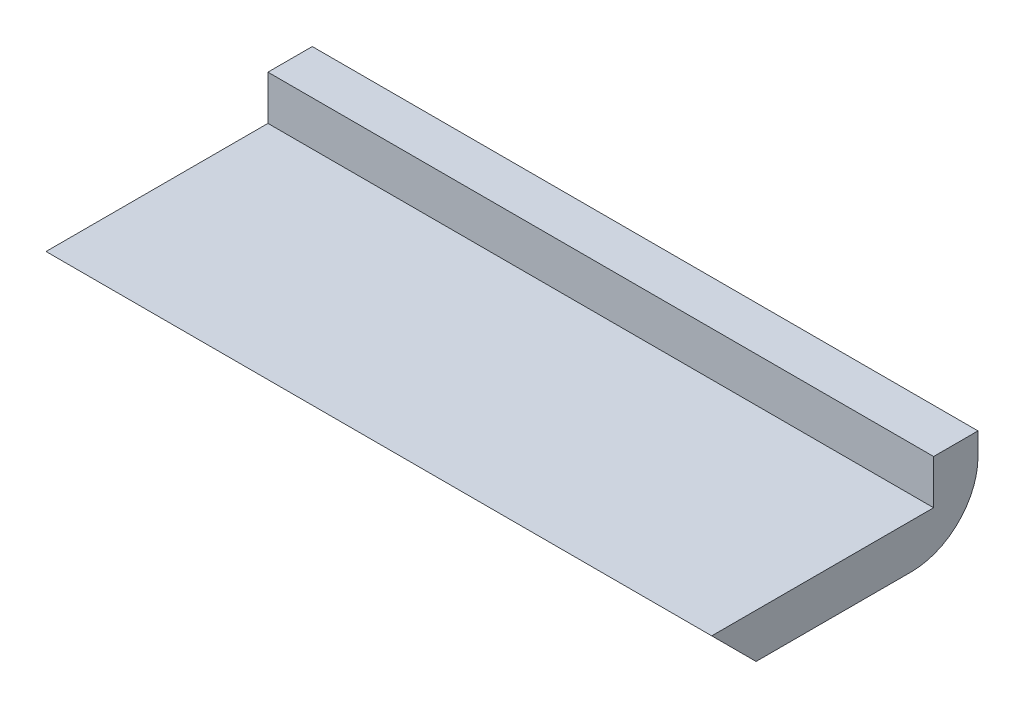
SolidWorks part; units mm, degrees
ref_plane "Alzado" through (0, 0, 0) normal (0, 0, 1) x (1, 0, 0)
ref_plane "Planta" through (0, 0, 0) normal (0, 1, 0) x (1, 0, 0)
ref_plane "Vista lateral" through (0, 0, 0) normal (1, 0, 0) x (0, 0, -1)
sketch "Croquis1" plane through (0, 0, 0) normal (0, 1, 0) x (1, 0, 0)
  line L1 (-15, -5) -> (15, -5)
  line L2 (-15, -5) -> (-15, 5)
  line L3 (-15, 5) -> (15, 5)
  line L4 (15, -5) -> (15, 5)
  line L5 (-15, -5) -> (15, 5) construction
  line L6 (-15, 5) -> (15, -5) construction
  point P0 (0, 0)
extrude "Saliente-Extruir1" add sketch "Croquis1" along normal blind 2
sketch "Croquis2" plane through (0, 2, 0) normal (0, 1, 0) x (1, 0, 0)
  line L1 (-15, 5) -> (15, 5)
  line L2 (-15, 5) -> (-15, 7)
  line L3 (-15, 7) -> (15, 7)
  line L4 (15, 5) -> (15, 7)
extrude "Saliente-Extruir2" add sketch "Croquis2" along normal blind 2 and the other way blind 2
sketch "Croquis3" plane through (0, 0, 0) normal (0, -1, 0) x (1, 0, 0)
  line L0 (0, -7) -> (0, -5)
  line L1 (15, -7) -> (-15, -7) construction
  line L2 (0, 5) -> (0, 3)
  line L3 (-15, 5) -> (15, 5) construction
  line L4 (-13, 3) -> (13, 3)
  line L5 (13, 3) -> (13, -5)
  line L6 (13, -5) -> (-13, -5)
  line L7 (-13, -5) -> (-13, 3)
  line L8 (-108.2504, -345.5802) -> (-588.2504, -345.5802) construction
  line L9 (15, 5) -> (15, -7) construction
  line L10 (-15, -7) -> (-15, 5) construction
  line L11 (-107.2449, -345.9043) -> (-587.2449, -345.9043) construction
  line L12 (-13, -3.3986) -> (-13, 1.6832)
  line L13 (-13, 1.6832) -> (-11.8002, 1.6832)
  line L14 (-11.8002, 1.6832) -> (-9.5832, -1.3407)
  line L15 (-9.5832, -1.3407) -> (-10.2334, -2.2573)
  line L16 (-10.2334, -2.2573) -> (-11.7241, -0.2241)
  line L17 (-11.7241, -0.2241) -> (-11.7241, -3.3986)
  line L18 (-11.7241, -3.3986) -> (-13, -3.3986)
  line L19 (-8.709, 1.6832) -> (-7.5492, 1.6832)
  line L20 (-7.5492, 1.6832) -> (-7.5492, -3.3986)
  line L21 (-7.5492, -3.3986) -> (-8.83, -3.3986)
  line L22 (-8.83, -3.3986) -> (-8.83, -0.2241)
  line L23 (-8.83, -0.2241) -> (-9.3309, -0.9303)
  line L24 (-9.3309, -0.9303) -> (-9.9615, -0.0702)
  line L25 (-9.9615, -0.0702) -> (-8.709, 1.6832)
  line L26 (-6.6004, 1.6832) -> (-5.3492, 1.6832)
  line L27 (-5.3492, 1.6832) -> (-5.3492, -1.7252)
  line L28 (-1.4166, 1.6832) -> (-0.3542, 1.6832)
  line L29 (-0.3542, 1.6832) -> (3.0735, -2.8639)
  line L30 (-6.6004, 1.6832) -> (-6.6004, -1.7252)
  line L31 (-3.5616, 1.6832) -> (-2.3179, 1.6832)
  line L32 (-2.3179, 1.6832) -> (-2.3179, -1.7252)
  line L33 (-3.5616, 1.6832) -> (-3.5616, -1.7252)
  line L34 (3.0735, -2.8639) -> (3.0735, -3.4119)
  line L35 (3.0735, -3.4119) -> (2.0041, -3.4119)
  line L36 (2.0041, -3.4119) -> (-1.4166, 1.126)
  line L37 (-1.4166, 1.126) -> (-1.4166, 1.6832)
  line L38 (-1.4166, -3.4119) -> (-0.1476, -3.4119)
  line L39 (-0.1476, -3.4119) -> (-0.1476, -1.1658)
  line L40 (-0.1476, -1.1658) -> (-1.4166, 0.4548)
  line L41 (-1.4166, 0.4548) -> (-1.4166, -3.4119)
  line L42 (1.8742, 1.6832) -> (3.0735, 1.6832)
  line L43 (3.0735, 1.6832) -> (3.0735, -2.084)
  line L44 (3.0735, -2.084) -> (1.8742, -0.5524)
  line L45 (1.8742, -0.5524) -> (1.8742, 1.6832)
  line L46 (3.6686, -3.4119) -> (4.9713, -3.4119)
  line L47 (4.9713, -3.4119) -> (6.3156, 0.4548)
  line L48 (6.3156, 0.4548) -> (7.6163, -3.4119)
  line L49 (7.6163, -3.4119) -> (8.9191, -3.4119)
  line L50 (8.9191, -3.4119) -> (6.967, 1.6832)
  line L51 (6.967, 1.6832) -> (5.6424, 1.6832)
  line L52 (5.6424, 1.6832) -> (3.6686, -3.4119)
  line L53 (7.9726, 1.6832) -> (9.4686, 1.6832)
  line L54 (9.4686, 1.6832) -> (10.4427, -0.2241)
  line L55 (10.4427, -0.2241) -> (11.4805, 1.6832)
  line L56 (11.4805, 1.6832) -> (12.9511, 1.6832)
  line L57 (12.9511, 1.6832) -> (11.0485, -1.4603)
  line L58 (11.0485, -1.4603) -> (11.0485, -3.4119)
  line L59 (11.0485, -3.4119) -> (9.7446, -3.4119)
  line L60 (9.7446, -3.4119) -> (9.7446, -1.4603)
  line L61 (9.7446, -1.4603) -> (7.9726, 1.6832)
  arc A0 (-5.3492, -1.7252) -> (-3.5616, -1.7252) centre (-4.4554, -1.2839) ccw
  arc A1 (-6.6004, -1.7252) -> (-2.3179, -1.7252) centre (-4.4591, -1.2094) ccw
  point P12 (0, 3)
  point P76 (0, 0)
  point P77 (0, 0)
  dimension "D1" = 2
  dimension "D2" = 2
  dimension "D3" = 2
  dimension "D4" = 2
chamfer "Chaflán1" distance 2 angle 45 1 edges at (0, 0, 5)
fillet "Redondeo1" radius 3 1 edges at (0, 0, -7)
extrude "Cortar-Extruir1" cut sketch "Croquis3" against normal blind 1.3 contours L25 L24 L23 L22 L21 L20 L19 | L18 L17 L16 L15 L14 L13 L7 | L30 A1 L32 L31 L33 A0 L27 L26 | L40 L41 L38 L39 | L37 L36 L35 L34 L29 L28 | L45 L44 L43 L42 | L51 L52 L46 L47 L48 L49 L50 | L61 L60 L59 L58 L57 L56 L55 L54 L53 region at (-11.8401, 0, -0.7454) region at (-8.3806, 0, -0.6791) region at (-5.9748, 0, 1.6167) region at (0.8261, 0, -0.8655) region at (-0.8382, 0, -1.8479) region at (2.5248, 0, 0.15) region at (4.7237, 0, -0.8908) region at (10.421, 0, -0.3888)
